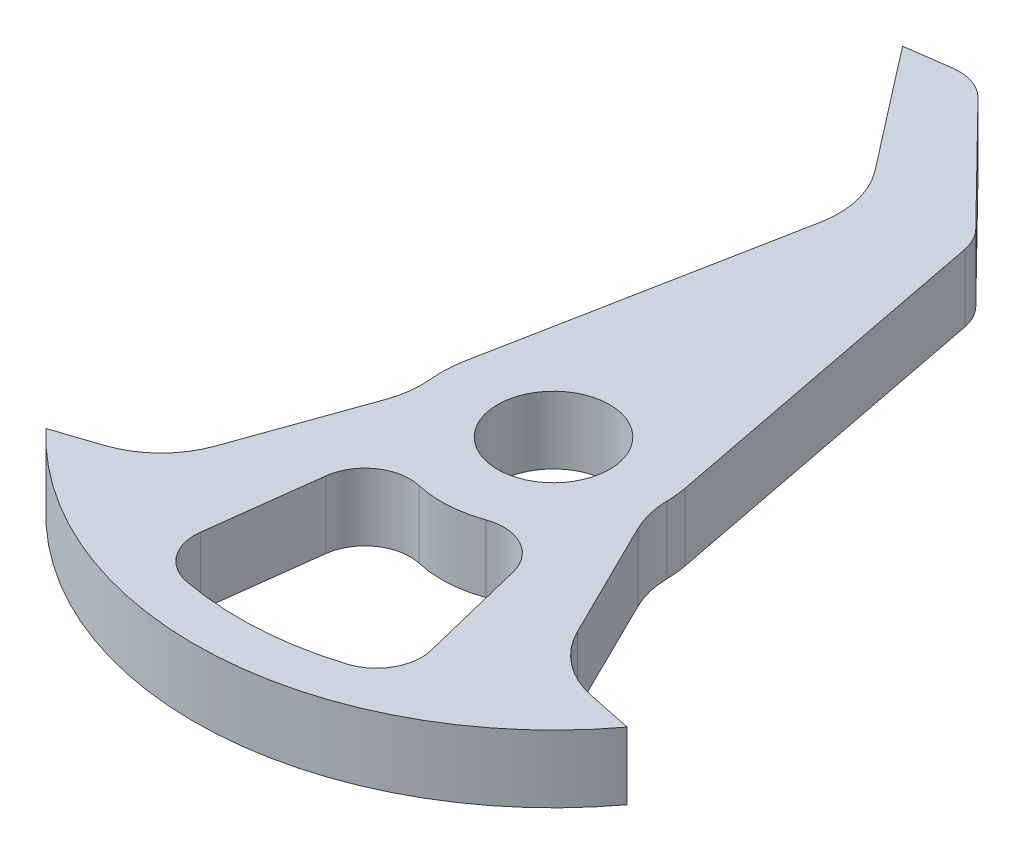
SolidWorks part; units mm, degrees
material "AISI Type A2 Tool Steel"
ref_plane "Front Plane" through (0, 0, 0) normal (0, 0, 1) x (1, 0, 0)
ref_plane "Top Plane" through (0, 0, 0) normal (0, 1, 0) x (1, 0, 0)
ref_plane "Right Plane" through (0, 0, 0) normal (1, 0, 0) x (0, 0, -1)
other "Center of Mass"
other "Bounding Box"
ref_plane "Default Plane" through (-8.9266, -12.7485, 0) normal (-0.1736, 0.9848, 0) x (0.9848, 0.1736, 0)
sketch "Sketch1" plane through (0, 0, 0) normal (0, 1, 0) x (1, 0, 0)
  line L0 (-15.5865, 3.0126) -> (-6.35, 50.8)
  line L1 (-6.35, 50.8) -> (-23.2013, 72.582)
  line L2 (15.5865, 3.0126) -> (6.35, 50.8)
  line L4 (-6.35, 50.8) -> (6.35, 50.8) construction
  line L5 (0, 50.8) -> (0, 0) construction
  line L6 (-23.2013, 72.582) -> (0, 0) construction
  line L7 (-23.2013, 72.582) -> (-13.7628, 73.8626)
  line L8 (-13.7628, 73.8626) -> (5.7363, 53.975)
  line L9 (5.7363, 53.975) -> (6.35, 50.8)
  circle A0 centre (0, 0) radius 7.9375
  arc A1 (-15.5865, 3.0126) -> (15.5865, 3.0126) centre (0, 0) ccw
  circle A2 centre (0, 0) radius 76.2 construction
  arc A4 (15.5865, 3.0126) -> (-15.5865, 3.0126) centre (0, 0) ccw construction
  dimension "D1" = 15.875
  dimension "D2" = 152.4
  dimension "D3" = 31.75
  dimension "D4" = 3.175
  dimension "D5" = 12.7
  dimension "D6" = 50.8
  dimension "D7" = 20
  dimension "D8" = 9.525
  dimension "D9" = 60
extrude "Boss-Extrude1" add sketch "Sketch1" along normal mid plane 9.525
fillet "Fillet6" radius 6.35 2 edges at (-13.7628, 0, -73.8626) (5.7363, 0, -53.975)
fillet "Fillet9" radius 12.7 1 edges at (-6.35, 0, -50.8)
sketch "Sketch2" plane through (0, 4.7625, 0) normal (0, 1, 0) x (1, 0, 0)
  line L0 (0, 0) -> (-1.4202, 24.3492) construction
  line L1 (-15.343, -4.0753) -> (-24.8926, -30.8684)
  line L2 (-24.8926, -30.8684) -> (-36.9477, -34.8642)
  line L3 (15.7127, -2.2639) -> (28.3126, -27.7651)
  line L4 (28.3126, -27.7651) -> (40.7504, -30.3323)
  line L5 (2.958, -50.7138) -> (0, 0) construction
  line L6 (-36.9477, -34.8642) -> (0, 0) construction
  line L7 (0, 0) -> (40.7504, -30.3323) construction
  line L8 (-36.9477, -34.8642) -> (1.9014, -32.5982) construction
  line L9 (1.9014, -32.5982) -> (40.7504, -30.3323) construction
  line L10 (-15.343, -4.0753) -> (15.7127, -2.2639) construction
  arc A0 (-15.5865, 3.0126) -> (15.5865, 3.0126) centre (0, 0) ccw construction
  arc A1 (-36.9477, -34.8642) -> (40.7504, -30.3323) centre (0, 0) ccw
  circle A2 centre (0, 0) radius 76.2 construction
  arc A3 (-15.343, -4.0753) -> (15.7127, -2.2639) centre (0, 0) ccw
  dimension "D1" = 25.4
  dimension "D2" = 25
  dimension "D3" = 25
  dimension "D4" = 100
  dimension "D5" = 3.175
  dimension "D6" = 12.7
extrude "Boss-Extrude2" add sketch "Sketch2" against normal up to surface (9.525 mm away) up to face at (-6.3228, -4.7625, -45.9675)
sketch "Sketch3" plane through (0, 4.7625, 0) normal (0, 1, 0) x (1, 0, 0)
  line L0 (-10.2487, -12.1235) -> (-14.0024, -42.1869)
  line L1 (11.5887, -10.8498) -> (18.8121, -40.2729)
  line L2 (-15.343, -4.0753) -> (-10.2487, -12.1235) construction
  line L3 (11.5887, -10.8498) -> (15.7127, -2.2639) construction
  line L4 (-15.343, -4.0753) -> (-24.8926, -30.8684) construction
  arc A0 (11.5887, -10.8498) -> (-10.2487, -12.1235) centre (0, 0) cw
  arc A1 (-15.5865, 3.0126) -> (15.5865, 3.0126) centre (0, 0) ccw construction
  arc A2 (-14.0024, -42.1869) -> (18.8121, -40.2729) centre (0, 0) ccw
  arc A3 (-36.9477, -34.8642) -> (40.7504, -30.3323) centre (0, 0) ccw construction
  point P16 (18.1592, -40.5715)
  point P17 (-14.0024, -41.5548)
  dimension "D1" = 6.35
  dimension "D2" = 12.5
  dimension "D3" = 9.525
extrude "Cut-Extrude1" cut sketch "Sketch3" against normal through all
fillet "Fillet7" radius 6.35 4 edges at (18.8121, 0, 40.2729) (11.5887, 0, 10.8498) (-10.2487, 0, 12.1235) (-14.0024, 0, 42.1869)
fillet "Fillet8" radius 12.7 4 edges at (28.3126, 0, 27.7651) (15.7127, 0, 2.2639) (-15.343, 0, 4.0753) (-24.8926, 0, 30.8684)
